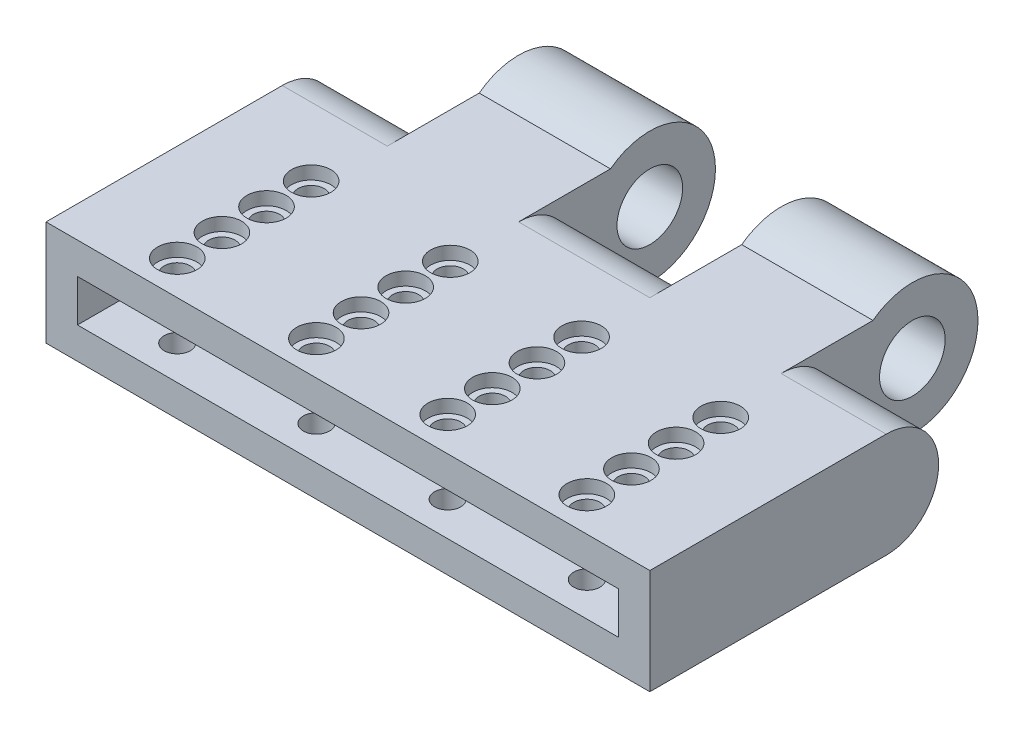
SolidWorks part; units mm, degrees
ref_plane "Front Plane" through (0, 0, 0) normal (0, 0, 1) x (1, 0, 0)
ref_plane "Top Plane" through (0, 0, 0) normal (0, 1, 0) x (1, 0, 0)
ref_plane "Right Plane" through (0, 0, 0) normal (1, 0, 0) x (0, 0, -1)
sketch "Sketch2" plane through (0, 0, 0) normal (0, 0, 1) x (1, 0, 0)
  line L1 (0, 0) -> (230, 0)
  line L2 (0, 0) -> (0, 40)
  line L3 (0, 40) -> (230, 40)
  line L4 (230, 0) -> (230, 40)
extrude "Boss-Extrude1" add sketch "Sketch2" along normal blind 80
ref_plane "Plane1" through (115, 0, 0) normal (1, 0, 0) x (0, 0, -1)
ref_plane "Plane2" through (140, 0, 0) normal (1, 0, 0) x (0, 0, -1)
sketch "Sketch6" plane through (140, 0, 0) normal (1, 0, 0) x (0, 0, -1)
  circle A0 centre (10, 20) radius 25
extrude "Boss-Extrude3" add sketch "Sketch6" along normal blind 50 contours A0
sketch "Sketch7" plane through (140, 0, 0) normal (-1, 0, 0) x (0, 0, 1)
  circle A0 centre (-10, 20) radius 12.5
extrude "Cut-Extrude2" cut sketch "Sketch7" against normal blind 50
sketch "Sketch8" plane through (140, 0, 0) normal (-1, 0, 0) x (0, 0, 1)
  circle A0 centre (-10, 20) radius 26.5
extrude "Cut-Extrude3" cut sketch "Sketch8" along normal blind 25
sketch "Sketch11" plane through (190, 0, 0) normal (1, 0, 0) x (0, 0, -1)
  circle A0 centre (10, 20) radius 26.5
extrude "Cut-Extrude4" cut sketch "Sketch11" along normal blind 40
mirror "Mirror1" about plane through (115, 0, 0) normal (1, 0, 0) of "Cut-Extrude4", "Cut-Extrude3", "Cut-Extrude2", "Boss-Extrude3"
sketch "Sketch12" plane through (230, 0, 0) normal (1, 0, 0) x (0, 0, -1)
  line L0 (-80, 0) -> (-80, 40) construction
  line L1 (-80, 20) -> (-16.4749, 20)
  line L2 (-80, 20) -> (-80, 0)
  line L3 (-80, 0) -> (-16.4749, 0)
  line L4 (-16.4749, 20) -> (-16.4749, 0)
  line L5 (-80, 0) -> (-7.3853, 0) construction
ref_plane "Plane3" through (65, 0, 0) normal (1, 0, 0) x (0, 0, -1)
ref_plane "Plane4" through (165, 0, 0) normal (-1, 0, 0) x (0, 0, 1)
sketch "Sketch14" plane through (90, 0, 0) normal (1, 0, 0) x (0, 0, -1)
  line L0 (-80, 0) -> (-16.4749, 0) construction
  line L1 (-7.3853, 40) -> (-20, 40)
  line L2 (-7.3853, 40) -> (-7.3853, 0)
  line L3 (-7.3853, 0) -> (-20, 0)
  line L4 (-20, 40) -> (-20, 0)
extrude "Cut-Extrude6" cut sketch "Sketch14" along normal blind 50
fillet "Fillet3" radius 20 2 edges at (115, 40, 20) (115, 0, 20)
mirror "Mirror5" about plane through (165, 0, 0) normal (-1, 0, 0) of "Cut-Extrude6", "Fillet3"
mirror "Mirror8" about plane through (65, 0, 0) normal (1, 0, 0) of "Fillet3", "Cut-Extrude6"
sketch "Sketch15" plane through (0, 0, 80) normal (0, 0, 1) x (1, 0, 0)
  line L1 (0, 40) -> (230, 40)
  line L2 (0, 40) -> (0, 0)
  line L3 (0, 0) -> (230, 0)
  line L4 (230, 40) -> (230, 0)
extrude "Boss-Extrude4" add sketch "Sketch15" along normal blind 50
sketch "Sketch18" plane through (0, 0, 130) normal (0, 0, 1) x (1, 0, 0)
  line L0 (0, 40) -> (0, 0) construction
  line L1 (12, 12) -> (218, 12)
  line L2 (12, 12) -> (12, 28)
  line L3 (12, 28) -> (218, 28)
  line L4 (218, 12) -> (218, 28)
  line L5 (230, 20) -> (230, 0) construction
  line L6 (0, 0) -> (230, 0) construction
  line L7 (230, 40) -> (0, 40) construction
  dimension "D1" = 12
  dimension "D2" = 12
  dimension "D3" = 12
  dimension "D4" = 12
extrude "Cut-Extrude7" cut sketch "Sketch18" against normal blind 80
sketch "Sketch21" plane through (0, 40, 0) normal (0, 1, 0) x (1, 0, 0)
  line L0 (12, -50) -> (12, -130) construction
  line L1 (218, -50) -> (12, -50) construction
  circle A0 centre (37, -66) radius 7.5
  dimension "D1" = 25
  dimension "D2" = 16
extrude "Cut-Extrude8" cut sketch "Sketch21" against normal blind 5
sketch "Sketch22" plane through (0, 35, 0) normal (0, 1, 0) x (1, 0, 0)
  circle A0 centre (37, -66) radius 5
extrude "Cut-Extrude9" cut sketch "Sketch22" against normal blind 35
ref_plane "Plane5" through (63.5, 0, 0) normal (1, 0, 0) x (0, 0, -1)
pattern_linear "LPattern1" count 4 spacing 17 along (0, 0, 1) of "Cut-Extrude8", "Cut-Extrude9"
mirror "Mirror9" about plane through (63.5, 0, 0) normal (1, 0, 0) of "LPattern1", "Cut-Extrude9", "Cut-Extrude8"
mirror "Mirror10" about plane through (115, 0, 0) normal (1, 0, 0) of "Mirror9", "LPattern1"
